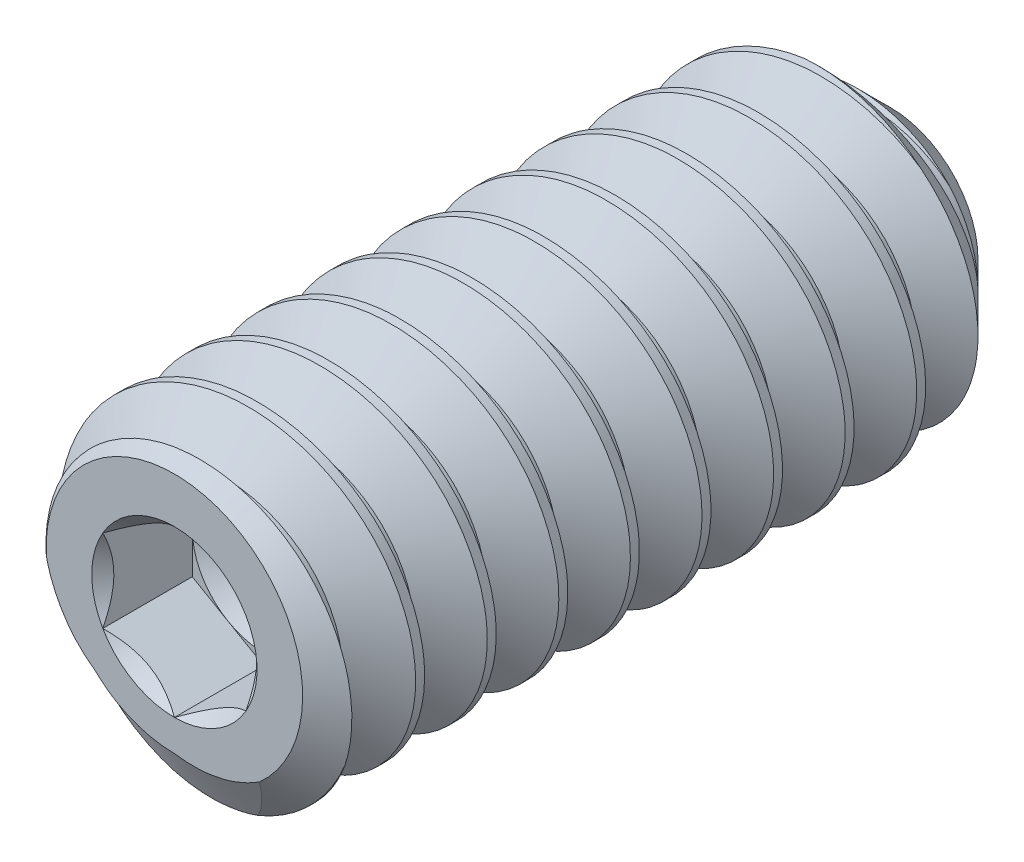
SolidWorks part; units mm, degrees
ref_plane "Front" through (0, 0, 0) normal (0, 0, 1) x (1, 0, 0)
ref_plane "Top" through (0, 0, 0) normal (0, 1, 0) x (1, 0, 0)
ref_plane "Right" through (0, 0, 0) normal (1, 0, 0) x (0, 0, -1)
sketch "Sketch22" plane through (0, 0, 0) normal (1, 0, 0) x (0, 0, -1)
  line L0 (-2.9408, 0) -> (-2.9408, 1.1379)
  line L1 (-2.9408, 1.1379) -> (-2.7416, 1.4224)
  line L2 (-2.7416, 1.4224) -> (2.7662, 1.4224)
  line L3 (2.7662, 1.4224) -> (3.4092, 0.7794)
  line L4 (3.4092, 0.7794) -> (2.9408, 0)
  line L5 (2.9408, 0) -> (-2.9408, 0)
  line L6 (2.9408, 0) -> (3.4092, 0) construction
  line L7 (3.4092, 0) -> (3.4092, 0.7794) construction
  line L8 (3.4092, -0.7794) -> (2.9408, 0) construction
  line L9 (-2.7416, -1.4224) -> (2.7662, -1.4224) construction
  dimension "Dia" = 2.8448
  dimension "Length" = 6.35
  dimension "D3" = 35
  dimension "D5" = 118
  dimension "D6" = 45
  dimension "D7" = 2.2758
revolve "Revolve1" add sketch "Sketch22" angle 360 about L6
ref_plane "Plane1" through (0, 0, -3.4092) normal (0, 0, 1) x (1, 0, 0)
sketch "Sketch27" plane through (0, 0, -3.4092) normal (0, 0, 1) x (1, 0, 0)
  circle A0 centre (0, 0) radius 1.4224 construction
  circle A1 centre (0, 0) radius 1.4224
curve "Helix/Spiral1" pitch 0.635 height 6.985 radius 1.4224 centre (0, 0, -3.4092) axis (0, 0, 1) start towards (0, 1, 0)
sketch "Sketch28" plane through (0, 0, 0) normal (1, 0, 0) x (0, 0, -1)
  line L0 (3.4092, 1.4224) -> (3.9648, 1.4224)
  line L1 (3.9648, 1.4224) -> (3.7267, 1.01)
  line L2 (3.7267, 1.01) -> (3.6473, 1.01)
  line L3 (3.6473, 1.01) -> (3.4092, 1.4224)
  line L4 (3.5282, 1.2162) -> (3.8457, 1.2162) construction
  line L6 (-2.7416, 1.4224) -> (2.7662, 1.4224) construction
  line L7 (3.4092, 1.5646) -> (3.4092, -1.5646) construction
  dimension "D1" = 0.0794
  dimension "D2" = 0.3175
  dimension "D3" = 60
sweep "Cut-Sweep2" cut profiles "Sketch28" path "Helix/Spiral1"
sketch "Sketch23" plane through (0, 0, 2.9408) normal (0, 0, 1) x (1, 0, 0)
  line L1 (0, 0.7332) -> (-0.635, 0.3666)
  line L2 (-0.635, 0.3666) -> (-0.635, -0.3666)
  line L3 (-0.635, -0.3666) -> (0, -0.7332)
  line L4 (0, -0.7332) -> (0.635, -0.3666)
  line L5 (0.635, -0.3666) -> (0.635, 0.3666)
  line L6 (0.635, 0.3666) -> (0, 0.7332)
  circle A0 centre (0, 0) radius 0.635 construction
  dimension "Hex" = 1.27
extrude "Cut-Extrude10" cut sketch "Sketch23" against normal blind 0.7937
sketch "Sketch24" plane through (0, 0, 2.9408) normal (0, 0, 1) x (1, 0, 0)
  circle A0 centre (0, 0) radius 0.7332
extrude "Cut-Extrude11" cut sketch "Sketch24" against normal through all draft 45
sketch "Sketch26" plane through (0, 0, 2.1471) normal (0, 0, 1) x (1, 0, 0)
  circle A0 centre (0, 0) radius 0.635 construction
  circle A1 centre (0, 0) radius 0.635
extrude "Cut-Extrude12" cut sketch "Sketch26" against normal through all draft 60
sketch "Sketch30" plane through (0, 0, 0) normal (1, 0, 0) x (0, 0, -1)
  line L0 (-2.7416, 1.4224) -> (2.7662, 1.4224) construction
  line L1 (-2.9408, 0) -> (-2.9408, 1.1379) construction
  line L2 (3.4092, 0) -> (3.4092, 0.7794) construction
  line L3 (-2.7416, -1.4224) -> (2.7662, -1.4224) construction
  point P0 (-2.9408, 1.4224)
  point P1 (3.4092, 1.4224)
  point P2 (3.4092, -1.4224)
  point P11 (1.1867, -1.4224)
  dimension "D1" = 2.2225
sketch "Sketch31" plane through (0, 0, 0) normal (1, 0, 0) x (0, 0, -1)
  line L2 (2.9408, 0) -> (3.4092, -0.7794)
  line L3 (3.4092, 0.7794) -> (2.9408, 0)
equation "\"D7@Sketch22\"=\"Dia@Sketch22\"*.8"
equation "\"D1@Sketch28\" = \"D4@Helix/Spiral1\" * .125"
equation "\"D3@Helix/Spiral1\" = \"Length@Sketch22\" + \"D4@Helix/Spiral1\""
equation "\"D1@Sketch30\" = \"D4@Helix/Spiral1\" * 3.5"
equation "\"hex Depth@Cut-Extrude10\" = \"Hex@Sketch23\" * .625"
equation "\"D2@Sketch28\" = \"D4@Helix/Spiral1\" * .5"
